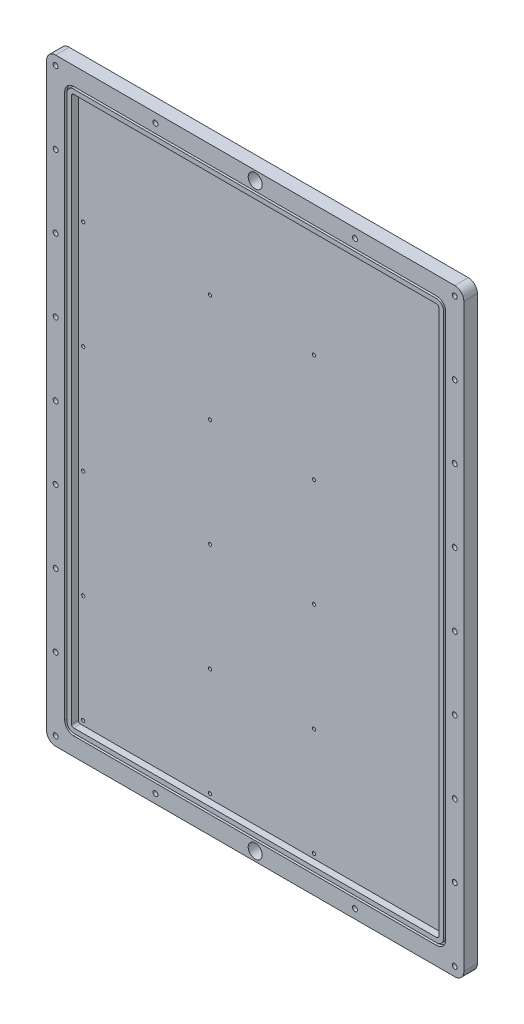
SolidWorks part; units mm, degrees
ref_plane "Front Plane" through (0, 0, 0) normal (0, 0, 1) x (1, 0, 0)
ref_plane "Top Plane" through (0, 0, 0) normal (0, 1, 0) x (1, 0, 0)
ref_plane "Right Plane" through (0, 0, 0) normal (1, 0, 0) x (0, 0, -1)
sketch "Sketch1" plane through (0, 0, 0) normal (0, 0, 1) x (1, 0, 0)
  line L1 (0, 0) -> (292.1, 0)
  line L2 (0, 0) -> (0, 419.1)
  line L3 (0, 419.1) -> (292.1, 419.1)
  line L4 (292.1, 0) -> (292.1, 419.1)
  dimension "D1" = 419.1
  dimension "D2" = 292.1
extrude "Boss-Extrude1" add sketch "Sketch1" along normal blind 9.525
sketch "Sketch4" plane through (0, 0, 9.525) normal (0, 0, 1) x (1, 0, 0)
  line L3 (0, 419.1) -> (0, 0) construction
  line L4 (6.35, 412.75) -> (285.75, 412.75) construction
  line L5 (6.35, 412.75) -> (6.35, 6.35) construction
  line L6 (6.35, 6.35) -> (285.75, 6.35) construction
  line L7 (285.75, 412.75) -> (285.75, 6.35) construction
  line L8 (292.1, 419.1) -> (0, 419.1) construction
  line L9 (292.1, 0) -> (292.1, 419.1) construction
  line L10 (0, 0) -> (292.1, 0) construction
  circle A0 centre (6.35, 6.35) radius 1.7272
  circle A1 centre (6.35, 412.75) radius 1.7272
  circle A2 centre (285.75, 412.75) radius 1.7272
  circle A3 centre (285.75, 6.35) radius 1.7272
  dimension "D5" = 3.4544
  dimension "D1" = 6.35
  dimension "D2" = 6.35
  dimension "D3" = 6.35
  dimension "D4" = 6.35
extrude "Cut-Extrude1" cut sketch "Sketch4" against normal through all
sketch "Sketch5" plane through (0, 0, 9.525) normal (0, 0, 1) x (1, 0, 0)
  line L0 (0, 419.1) -> (0, 0) construction
  line L1 (19.05, 406.4) -> (273.05, 406.4)
  line L2 (12.7, 400.05) -> (12.7, 19.05)
  line L3 (19.05, 12.7) -> (273.05, 12.7)
  line L4 (279.4, 400.05) -> (279.4, 19.05)
  line L5 (292.1, 419.1) -> (0, 419.1) construction
  line L6 (292.1, 0) -> (292.1, 419.1) construction
  line L7 (0, 0) -> (292.1, 0) construction
  line L8 (19.05, 14.2875) -> (273.05, 14.2875)
  line L9 (14.2875, 400.05) -> (14.2875, 19.05)
  line L10 (19.05, 404.8125) -> (273.05, 404.8125)
  line L11 (277.8125, 400.05) -> (277.8125, 19.05)
  arc A0 (273.05, 12.7) -> (279.4, 19.05) centre (273.05, 19.05) ccw
  arc A1 (12.7, 19.05) -> (19.05, 12.7) centre (19.05, 19.05) ccw
  arc A2 (273.05, 406.4) -> (279.4, 400.05) centre (273.05, 400.05) cw
  arc A3 (19.05, 406.4) -> (12.7, 400.05) centre (19.05, 400.05) ccw
  arc A4 (14.2875, 19.05) -> (19.05, 14.2875) centre (19.05, 19.05) ccw
  arc A5 (19.05, 404.8125) -> (14.2875, 400.05) centre (19.05, 400.05) ccw
  arc A6 (273.05, 404.8125) -> (277.8125, 400.05) centre (273.05, 400.05) cw
  arc A7 (273.05, 14.2875) -> (277.8125, 19.05) centre (273.05, 19.05) ccw
  dimension "D5" = 6.35
  dimension "D1" = 12.7
  dimension "D2" = 12.7
  dimension "D3" = 12.7
  dimension "D4" = 12.7
  dimension "D6" = 1.5875
  dimension "D7" = 1.5875
extrude "Cut-Extrude2" cut sketch "Sketch5" against normal blind 2.032 contours L1 A3 L2 A1 L3 A0 L4 A2 A7 L8 A4 L9 A5 L10 A6 L11 region at (146.05, 405.9245, 9.525)
pattern_linear "LPattern3" count 4 spacing 69.85 along (1, 0, 0) of face at (8.0772, 412.75, 0) of face at (8.0772, 6.35, 0)
pattern_linear "LPattern4" count 8 spacing 50.8 along (0, -1, 0) of face at (8.0772, 412.75, 0) of face at (287.4772, 412.75, 0)
sketch "Sketch6" plane through (0, 0, 9.525) normal (0, 0, 1) x (1, 0, 0)
  line L8 (274.6375, 19.05) -> (274.6375, 400.05)
  line L9 (273.05, 401.6375) -> (19.05, 401.6375)
  line L10 (17.4625, 400.05) -> (17.4625, 19.05)
  line L11 (19.05, 17.4625) -> (273.05, 17.4625)
  line L12 (274.6375, 19.05) -> (274.6375, 400.05)
  line L13 (273.05, 401.6375) -> (19.05, 401.6375)
  line L14 (17.4625, 400.05) -> (17.4625, 19.05)
  line L15 (19.05, 17.4625) -> (273.05, 17.4625)
  arc A8 (273.05, 17.4625) -> (274.6375, 19.05) centre (273.05, 19.05) ccw
  arc A9 (274.6375, 400.05) -> (273.05, 401.6375) centre (273.05, 400.05) ccw
  arc A10 (19.05, 401.6375) -> (17.4625, 400.05) centre (19.05, 400.05) ccw
  arc A11 (17.4625, 19.05) -> (19.05, 17.4625) centre (19.05, 19.05) ccw
  arc A12 (273.05, 17.4625) -> (274.6375, 19.05) centre (273.05, 19.05) ccw
  arc A13 (274.6375, 400.05) -> (273.05, 401.6375) centre (273.05, 400.05) ccw
  arc A14 (19.05, 401.6375) -> (17.4625, 400.05) centre (19.05, 400.05) ccw
  arc A15 (17.4625, 19.05) -> (19.05, 17.4625) centre (19.05, 19.05) ccw
  dimension "D1" = 3.175
extrude "Cut-Extrude3" cut sketch "Sketch6" against normal blind 4.7625
sketch "Sketch7" plane through (0, 0, 4.7625) normal (0, 0, 1) x (1, 0, 0)
  line L0 (273.05, 401.6375) -> (19.05, 401.6375) construction
  line L1 (20.8661, 398.4625) -> (271.2339, 398.4625) construction
  line L2 (20.8661, 398.4625) -> (20.8661, 20.6375) construction
  line L3 (20.8661, 20.6375) -> (271.2339, 20.6375) construction
  line L4 (271.2339, 398.4625) -> (271.2339, 20.6375) construction
  line L5 (17.4625, 400.05) -> (17.4625, 19.05) construction
  line L6 (274.6375, 19.05) -> (274.6375, 400.05) construction
  line L7 (19.05, 17.4625) -> (273.05, 17.4625) construction
  line L8 (17.4625, 400.05) -> (17.4625, 19.05) construction
  line L9 (274.6375, 19.05) -> (274.6375, 400.05) construction
  circle A0 centre (20.8661, 398.4625) radius 1.1303
  circle A1 centre (271.2339, 398.4625) radius 1.1303
  circle A2 centre (20.8661, 20.6375) radius 1.1303
  circle A3 centre (109.6645, 20.6375) radius 1.1303
  circle A4 centre (109.6645, 398.4625) radius 1.1303
  circle A5 centre (182.4355, 398.4625) radius 1.1303
  circle A6 centre (182.4355, 20.6375) radius 1.1303
  circle A7 centre (271.2339, 20.6375) radius 1.1303
  dimension "D5" = 2.2606
  dimension "D1" = 3.175
  dimension "D2" = 3.4036
  dimension "D3" = 3.4036
  dimension "D4" = 3.175
  dimension "D6" = 92.202
  dimension "D7" = 92.202
  dimension "D8" = 88.7984
  dimension "D9" = 88.7984
extrude "Cut-Extrude4" cut sketch "Sketch7" against normal blind 3.175
sketch "Sketch8" plane through (0, 0, 9.525) normal (0, 0, 1) x (1, 0, 0)
  circle A0 centre (146.05, 412.75) radius 4.9022
  circle A1 centre (146.05, 6.35) radius 4.9022
  dimension "D1" = 9.8044
extrude "Cut-Extrude5" cut sketch "Sketch8" against normal through all
fillet "Fillet1" radius 6.35 4 edges at (292.1, 0, 4.7625) (0, 0, 4.7625) (292.1, 419.1, 4.7625) (0, 419.1, 4.7625)
pattern_linear "LPattern10" count 5 spacing 75.565 along (0, -1, 0) of "Cut-Extrude4"
